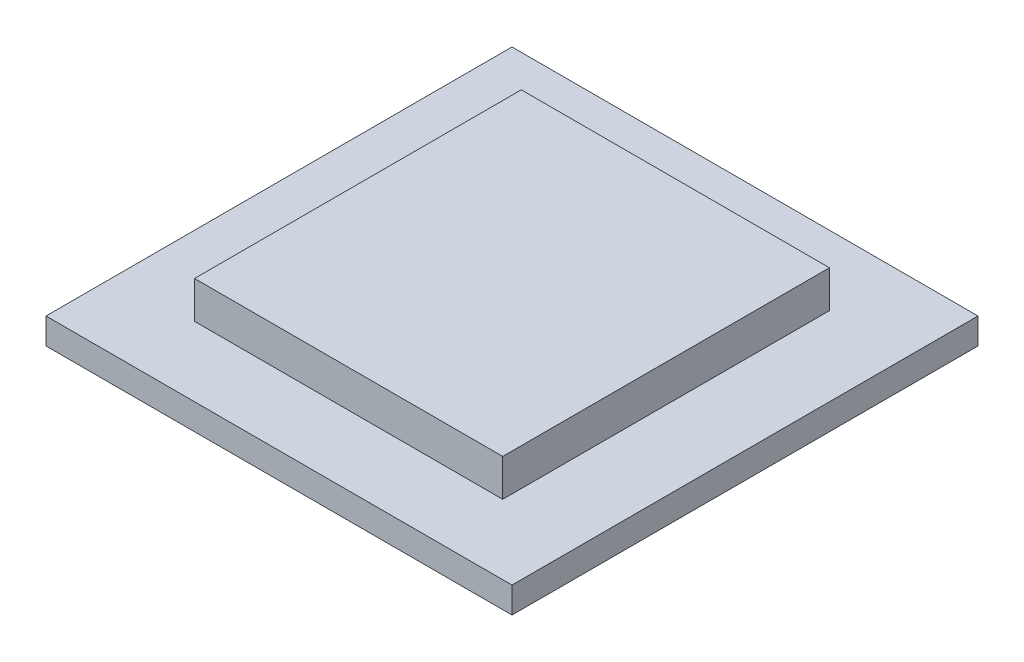
SolidWorks part; units mm, degrees
ref_plane "Front Plane" through (0, 0, 0) normal (0, 0, 1) x (1, 0, 0)
ref_plane "Top Plane" through (0, 0, 0) normal (0, 1, 0) x (1, 0, 0)
ref_plane "Right Plane" through (0, 0, 0) normal (1, 0, 0) x (0, 0, -1)
sketch "Sketch1" plane through (0, 0, 0) normal (0, 1, 0) x (1, 0, 0)
  line L1 (-8.3, -8.8) -> (8.3, -8.8)
  line L2 (-8.3, -8.8) -> (-8.3, 8.8)
  line L3 (-8.3, 8.8) -> (8.3, 8.8)
  line L4 (8.3, -8.8) -> (8.3, 8.8)
  line L5 (-8.3, -8.8) -> (8.3, 8.8) construction
  line L6 (-8.3, 8.8) -> (8.3, -8.8) construction
  line L7 (-12.55, -12.55) -> (12.55, -12.55)
  line L8 (-12.55, -12.55) -> (-12.55, 12.55)
  line L9 (-12.55, 12.55) -> (12.55, 12.55)
  line L10 (12.55, -12.55) -> (12.55, 12.55)
  line L11 (-12.55, -12.55) -> (12.55, 12.55) construction
  line L12 (-12.55, 12.55) -> (12.55, -12.55) construction
  point P0 (0, 0)
  point P5 (0, 0)
  dimension "D1" = 17.6
  dimension "D2" = 16.6
  dimension "D3" = 25.1
extrude "Boss-Extrude1" add sketch "Sketch1" along normal blind 2 contours L2 L3 L4 L1
extrude "Boss-Extrude2" add sketch "Sketch1<4>" against normal blind 1.4 contours L7 L10 L9 L8
sketch "Sketch1<4>" plane through (0, 0, 0) normal (0, 1, 0) x (1, 0, 0) same geometry as "Sketch1"
equation "\"D1@Sketch1\"=18-0.4"
equation "\"D2@Sketch1\"=17-0.4"
